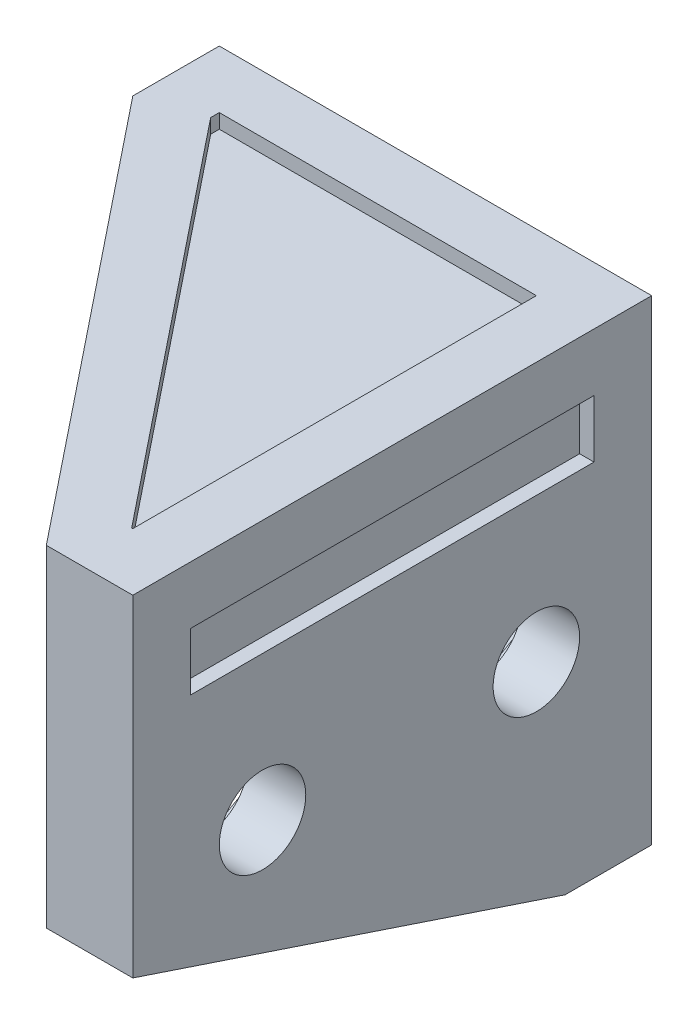
SolidWorks part; units mm, degrees
ref_plane "Front Plane" through (0, 0, 0) normal (0, 0, 1) x (1, 0, 0)
ref_plane "Top Plane" through (0, 0, 0) normal (0, 1, 0) x (1, 0, 0)
ref_plane "Right Plane" through (0, 0, 0) normal (1, 0, 0) x (0, 0, -1)
sketch "Sketch1" plane through (0, 0, 0) normal (0, 0, 1) x (1, 0, 0)
  line L1 (-3.9, -7.5) -> (7.5, -7.5)
  line L2 (-7.5, -3.9) -> (-7.5, 7.5)
  line L3 (-7.5, 7.5) -> (7.5, 7.5)
  line L4 (7.5, -7.5) -> (7.5, 7.5)
  line L5 (-7.5, -7.5) -> (7.5, 7.5) construction
  line L6 (-7.5, 7.5) -> (7.5, -7.5) construction
  arc A0 (-3.9, -7.5) -> (-7.5, -3.9) centre (-3.9, -3.9) cw
  point P0 (0, 0)
  dimension "D3" = 3.6
  dimension "D1" = 15
  dimension "D2" = 15
extrude "Boss-Extrude1" add sketch "Sketch1" along normal blind 3
sketch "Sketch2" plane through (7.5, 0, 0) normal (1, 0, 0) x (0, 0, -1)
  line L0 (-3, -7.5) -> (0, -7.5)
  line L1 (0, 7.5) -> (-18, 7.5)
  line L2 (0, 7.5) -> (0, -7.5)
  line L3 (-3, -7.5) -> (-18, -2.5)
  line L4 (-18, 7.5) -> (-18, -2.5)
  dimension "D1" = 18
  dimension "D2" = 5
extrude "Boss-Extrude2" add sketch "Sketch2" against normal blind 3
sketch "Sketch7" plane through (0, 7.5, 0) normal (0, 1, 0) x (1, 0, 0)
  line L0 (-7.5, -3) -> (4.5, -18)
  line L3 (-7.5, -3) -> (-7.5, 0)
  line L4 (-7.5, 0) -> (7.5, 0)
  line L5 (7.5, 0) -> (7.5, -18)
  line L6 (7.5, -18) -> (4.5, -18)
extrude "Boss-Extrude4" add sketch "Sketch7" along normal blind 1.5
hole_wizard "Ø4.0 (4) Diameter Hole1" positions "Sketch4" profile "Sketch3" hole size "Ø4.0" standard "Ansi Metric"
sketch "Sketch4" plane through (0, 0, 3) normal (0, 0, 1) x (1, 0, 0)
  line L0 (-1.5, 7.5) -> (-1.5, -7.5) construction
  line L1 (-3.9, -7.5) -> (4.5, -7.5) construction
  line L8 (-3.9, -7.5) -> (4.5, -7.5) construction
  line L9 (-7.5, 7.5) -> (4.5, 7.5) construction
  point P14 (-1.5, 4)
  point P16 (-1.5, -4)
  dimension "D1" = 8
  dimension "D2" = 3.5
sketch "Sketch3" plane through (-1.5, 4, 3) normal (1, 0, 0) x (0, -1, 0)
  line L0 (0, 0) -> (0, 6.2017)
  line L1 (0, 6.2017) -> (2, 5)
  line L2 (2, 5) -> (2, 0)
  line L5 (2, 0) -> (0, 0)
  line L10 (0, 6.2017) -> (-2, 5) construction
  line L11 (0, -6.35) -> (0, 107.95) construction
  dimension "Hole Dia." = 4
  dimension "Hole Depth" = 5
  dimension "Drill Angle" = 118
sketch "Sketch19" plane through (0, 0, 3) normal (0, 0, 1) x (1, 0, 0)
  line L4 (-4.6129, 6) -> (-6, 6)
  line L5 (3, 6) -> (1.6129, 6)
  line L8 (3, -6) -> (3, 6)
  line L9 (3, 6) -> (-6, 6)
  line L10 (-6, 6) -> (-6, -3.9)
  line L11 (-3.9, -6) -> (3, -6)
  line L12 (3, -6) -> (3, 6)
  line L14 (-6, 6) -> (-6, -3.9)
  line L15 (1.6129, -6) -> (3, -6)
  arc A2 (-4.7119, -5.8367) -> (1.6129, -6) centre (-1.5, -4) ccw
  arc A3 (-6, -3.9) -> (-3.9, -6) centre (-3.9, -3.9) ccw
  arc A4 (-6, -3.9) -> (-4.7119, -5.8367) centre (-3.9, -3.9) ccw
  arc A5 (1.6129, 6) -> (-4.6129, 6) centre (-1.5, 4) ccw
  dimension "D2" = 7.4
  dimension "D1" = 1.5
extrude "Cut-Extrude10" cut sketch "Sketch19" against normal blind 1
hole_wizard "Ø3.0 (3) Diameter Hole1" positions "Sketch6" profile "Sketch5" hole size "Ø3.0" standard "Ansi Metric" end condition through all
sketch "Sketch6" plane through (7.5, 0, 0) normal (1, 0, 0) x (0, 0, -1)
  line L0 (-3, -7.5) -> (0, -7.5) construction
  line L2 (0, -7.5) -> (0, 9) construction
  point P0 (-4, 0)
  point P2 (-13.5, 0)
  dimension "D1" = 7.5
  dimension "D2" = 9.5
  dimension "D3" = 4
sketch "Sketch5" plane through (7.5, 0, 4) normal (0, 1, 0) x (0, 0, -1)
  line L0 (0, 0) -> (0, 15)
  line L1 (0, 15) -> (1.5, 15)
  line L2 (1.5, 15) -> (1.5, 0)
  line L5 (1.5, 0) -> (0, 0)
  line L11 (0, -6.35) -> (0, 107.95) construction
  dimension "Thru Hole Dia." = 3
  dimension "Thru Hole Depth" = 15
sketch "Sketch14" plane through (4.5, 0, 0) normal (-1, 0, 0) x (0, 0, 1)
  circle A0 centre (4, 0) radius 3.5
  circle A1 centre (13.5, 0) radius 3.5
  dimension "D1" = 7
extrude "Cut-Extrude5" cut sketch "Sketch14" along normal blind 4
sketch "Sketch15" plane through (0, 9, 0) normal (0, 1, 0) x (1, 0, 0)
  line L5 (-5.5, -2) -> (-5.5, -2.2984)
  line L6 (-5.5, -2) -> (-5.5, -2.2984)
  line L11 (-5.5, -2.2984) -> (5.4612, -16)
  line L12 (5.4612, -16) -> (5.5, -16)
  line L13 (5.5, -16) -> (5.5, -2)
  line L14 (5.5, -2) -> (-5.5, -2)
  line L16 (-5.5, -2.2984) -> (5.4612, -16)
  line L17 (5.4612, -16) -> (5.5, -16)
  line L18 (5.5, -16) -> (5.5, -2)
  line L19 (5.5, -2) -> (-5.5, -2)
  dimension "D1" = 2
extrude "Cut-Extrude6" cut sketch "Sketch15" against normal blind 0.5
sketch "Sketch16" plane through (7.5, 0, 0) normal (1, 0, 0) x (0, 0, -1)
  line L0 (-18, 9) -> (0, 9) construction
  line L1 (-16, 7) -> (-2, 7)
  line L2 (-16, 7) -> (-16, 5)
  line L3 (-16, 5) -> (-2, 5)
  line L4 (-2, 7) -> (-2, 5)
  line L5 (-18, 9) -> (-18, -2.5) construction
  line L6 (0, -7.5) -> (0, 9) construction
  line L7 (-18.75, 3) -> (1.25, 3) construction
  dimension "D1" = 2
  dimension "D2" = 2
  dimension "D3" = 2
  dimension "D4" = 2
extrude "Cut-Extrude7" cut sketch "Sketch16" against normal blind 0.5
sketch "Sketch18" plane through (4.5, 0, 0) normal (-1, 0, 0) x (0, 0, 1)
  line L1 (16.25, -1.5877) -> (16.25, 1.5877)
  line L2 (16.25, 1.5877) -> (13.5, 3.1754)
  line L3 (13.5, 3.1754) -> (10.75, 1.5877)
  line L4 (10.75, 1.5877) -> (10.75, -1.5877)
  line L5 (10.75, -1.5877) -> (13.5, -3.1754)
  line L6 (13.5, -3.1754) -> (16.25, -1.5877)
  line L7 (6.75, -1.5877) -> (6.75, 1.5877)
  line L8 (6.75, 1.5877) -> (4, 3.1754)
  line L9 (4, 3.1754) -> (1.25, 1.5877)
  line L10 (1.25, 1.5877) -> (1.25, -1.5877)
  line L11 (1.25, -1.5877) -> (4, -3.1754)
  line L12 (4, -3.1754) -> (6.75, -1.5877)
  circle A0 centre (13.5, 0) radius 2.75 construction
  circle A1 centre (4, 0) radius 2.75 construction
  dimension "D1" = 5.5
extrude "Cut-Extrude9" cut sketch "Sketch18" against normal blind 1
fillet "Fillet1" radius 0.5 19 edges at (-5.6486, -5.063, 2) (3, -3.1531, 2.4808) (-6, 1.05, 2) (3, 4.4361, 2) (3, -4.6771, 3) (2.3064, -6, 3) (0.7831, -6.9116, 3) (-3.8575, -6.8517, 3) (-5.6486, -5.063, 3) (-6, -2.509, 3) (-6, 3.559, 3) (-5.3064, 6, 3) (-3.7831, 6.9116, 3) (3, 4.6771, 3) (-0.3, -7.5, 2.5) (-2.7, -7.5, 2.5) (0.7831, 6.9116, 3) (2.3064, 6, 2) (2.3064, 6, 3)
